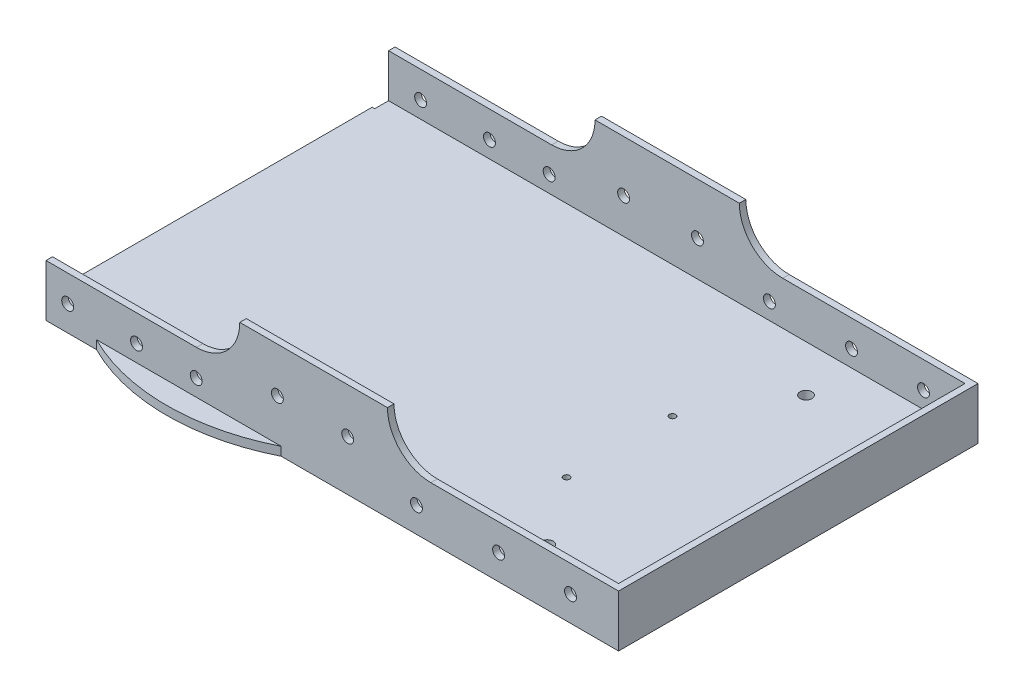
SolidWorks part; units mm, degrees
ref_plane "Front Plane" through (0, 0, 0) normal (0, 0, 1) x (1, 0, 0)
ref_plane "Top Plane" through (0, 0, 0) normal (0, 1, 0) x (1, 0, 0)
ref_plane "Right Plane" through (0, 0, 0) normal (1, 0, 0) x (0, 0, -1)
sketch "Sketch1" plane through (0, 0, 0) normal (0, 1, 0) x (1, 0, 0)
  line L1 (0, 0) -> (278.0499, 0)
  line L2 (0, 0) -> (0, 166.0007)
  line L3 (0, 166.0007) -> (278.0499, 166.0007)
  line L4 (278.0499, 0) -> (278.0499, 166.0007)
extrude "Boss-Extrude1" add sketch "Sketch1" along normal blind 24
sketch "Sketch2" plane through (0, 0, 0) normal (0, -1, 0) x (-1, 0, 0)
  line L1 (-7.6506, 156.6405) -> (14.2402, 156.6405)
  line L2 (-7.6506, 156.6405) -> (-7.6506, 11.5417)
  line L3 (-7.6506, 11.5417) -> (14.2402, 11.5417)
  line L4 (14.2402, 156.6405) -> (14.2402, 11.5417)
extrude "Cut-Extrude1" cut sketch "Sketch2" against normal through all
sketch "Sketch3" plane through (0, 24, 0) normal (0, 1, 0) x (1, 0, 0)
  line L0 (226.9955, 0) -> (226.9955, 3) construction
  line L1 (0, 0) -> (278.0499, 0) construction
  line L2 (278.0499, 166.0007) -> (278.0499, 163.0007) construction
  line L3 (278.0499, 0) -> (278.0499, 166.0007) construction
  line L4 (0, 155.7398) -> (3, 155.7398) construction
  line L5 (0, 166.0007) -> (0, 156.6405) construction
  line L6 (278.0499, 22.4963) -> (275.0499, 22.4963) construction
  line L7 (275.0499, 163.0007) -> (275.0499, 3)
  line L8 (275.0499, 3) -> (3, 3)
  line L9 (3, 3) -> (3, 163.0007)
  line L10 (3, 163.0007) -> (275.0499, 163.0007)
extrude "Cut-Extrude2" cut sketch "Sketch3" against normal blind 20
sketch "Sketch4" plane through (0, 24, 0) normal (0, 1, 0) x (1, 0, 0)
  line L0 (0, 0) -> (278.0499, 0) construction
  line L1 (171.3453, 0) -> (103.1403, 0)
  line L2 (171.3453, 0) -> (171.3453, 3)
  line L3 (171.3453, 3) -> (103.1403, 3)
  line L4 (103.1403, 0) -> (103.1403, 3)
  line L5 (3, 3) -> (275.0499, 3) construction
extrude "Boss-Extrude2" add sketch "Sketch4" along normal blind 20
fillet "Fillet4" radius 20 1 edges at (103.1403, 24, -1.5) type face fillet first side face at (103.1403, 34, -1.5) second side face at (35.3801, 24, -4.8472)
fillet "Fillet5" radius 20 1 edges at (171.3453, 24, -1.5) type face fillet first side face at (145.489, 24, -97.7284) second side face at (171.3453, 34, -1.5)
sketch "Sketch5" plane through (0, 24, 0) normal (0, 1, 0) x (1, 0, 0)
  line L0 (278.0499, 166.0007) -> (0, 166.0007) construction
  line L1 (104.1867, 166.0007) -> (170.8443, 166.0007)
  line L2 (104.1867, 166.0007) -> (104.1867, 163.0007)
  line L3 (104.1867, 163.0007) -> (170.8443, 163.0007)
  line L4 (170.8443, 166.0007) -> (170.8443, 163.0007)
  line L5 (275.0499, 163.0007) -> (3, 163.0007) construction
extrude "Boss-Extrude3" add sketch "Sketch5" along normal blind 20
fillet "Fillet6" radius 20 1 edges at (104.1867, 24, -164.5007) type face fillet first side face at (104.1867, 34, -164.5007) second side face at (35.7289, 24, -161.8806)
fillet "Fillet7" radius 20 1 edges at (170.8443, 24, -164.5007) type face fillet first side face at (170.8443, 34, -164.5007) second side face at (228.8223, 24, -83.0003)
sketch "Sketch6" plane through (0, 0, -163.0007) normal (0, 0, 1) x (1, 0, 0)
  circle A0 centre (151.5064, 20.306) radius 2.75
  circle A1 centre (117.3926, 20.306) radius 2.75
extrude "HolesForBolts1" cut sketch "Sketch6" against normal through all
sketch "Sketch7" plane through (0, 0, -166.0007) normal (0, 0, -1) x (-1, 0, 0)
  circle A0 centre (-23.6542, 11.6758) radius 2.75
  circle A1 centre (-55.4415, 11.6758) radius 2.75
  circle A2 centre (-83.0044, 11.6758) radius 2.75
  circle A3 centre (-184.7276, 11.6758) radius 2.75
  circle A4 centre (-222.6455, 11.6758) radius 2.75
  circle A5 centre (-255.8817, 11.6758) radius 2.75
extrude "Cut-Extrude4" cut sketch "Sketch7" against normal through all
sketch "Sketch8" plane through (0, 0, -3) normal (0, 0, -1) x (-1, 0, 0)
  circle A0 centre (-120.4871, 23.2804) radius 2.75
  circle A1 centre (-152.9663, 23.2804) radius 2.75
extrude "Cut-Extrude5" cut sketch "Sketch8" against normal blind 20
ref_plane "Plane1" through (0, 0, -11.5417) normal (0, 0, 1) x (1, 0, 0)
sketch "Sketch11" plane through (0, 0, 0) normal (0, -1, 0) x (1, 0, 0)
  line L0 (7.6506, -11.5417) -> (0, -11.5417) construction
  line L1 (0, 0) -> (13.6461, 0)
  line L2 (0, 0) -> (0, -11.5417)
  line L3 (0, -11.5417) -> (13.6461, -11.5417)
  line L4 (13.6461, 0) -> (13.6461, -11.5417)
extrude "Cut-Extrude6" cut sketch "Sketch11" against normal through all
sketch "Sketch12" plane through (0, 0, 0) normal (0, -1, 0) x (1, 0, 0)
  line L0 (0, -156.6405) -> (7.6506, -156.6405) construction
  line L1 (0, -166.0007) -> (8.8441, -166.0007)
  line L2 (0, -166.0007) -> (0, -156.6405)
  line L3 (0, -156.6405) -> (8.8441, -156.6405)
  line L4 (8.8441, -166.0007) -> (8.8441, -156.6405)
extrude "Cut-Extrude7" cut sketch "Sketch12" against normal through all
sketch "HolesInLidForPiCover" plane through (0, 0, 0) normal (0, -1, 0) x (1, 0, 0)
  circle A0 centre (223.0138, -141.6086) radius 2.75
  circle A1 centre (223.0138, -22.1297) radius 2.75
extrude "Cut-Extrude8" cut sketch "HolesInLidForPiCover" against normal up to surface (4 mm away) up to face at (76.2977, 4, -83.5457)
ref_point "RasPiBoltPoint1"
ref_point "RasPiBoltPoint2"
ref_point "RasPiBoltPoint3"
ref_point "RasPiBoltPoint4"
sketch "LidHolesForPi" plane through (0, 0, 0) normal (0, -1, 0) x (1, 0, 0)
  circle A0 centre (200.5621, -102.3707) radius 1.455
  circle A1 centre (200.5621, -53.5029) radius 1.455
  circle A2 centre (258.5449, -53.5029) radius 1.455
  circle A3 centre (258.5449, -102.3707) radius 1.455
extrude "Cut-Extrude9" cut sketch "LidHolesForPi" against normal up to surface (4 mm away) up to face at (223.0138, 4, -24.8797)
ref_point "LidHoleForCoverLocation1"
ref_point "LidHoleForCoverLocation2"
sketch "Sketch14" plane through (0, 0, 0) normal (0, -1, 0) x (1, 0, 0)
  circle A0 centre (264.7636, -18.9201) radius 2.75
  circle A1 centre (181.6168, -18.9187) radius 2.75
extrude "Cut-Extrude10" cut sketch "Sketch14" against normal up to surface (4 mm away) up to face at (258.5449, 4, -54.9579)
sketch "Sketch15" plane through (0, 0, 0) normal (0, -1, 0) x (1, 0, 0)
  circle A0 centre (79.5908, -84.8811) radius 95
extrude "Boss-Extrude4" add sketch "Sketch15" against normal up to surface (4 mm away) up to face at (181.6168, 4, -21.6687)
sketch "Sketch16" plane through (0, 0, 0) normal (0, -1, 0) x (1, 0, 0)
  line L1 (7.6506, -22.8359) -> (-30.4108, -22.8359)
  line L2 (7.6506, -22.8359) -> (7.6506, -147.5505)
  line L3 (7.6506, -147.5505) -> (-30.4108, -147.5505)
  line L4 (-30.4108, -22.8359) -> (-30.4108, -147.5505)
extrude "Cut-Extrude11" cut sketch "Sketch16" against normal up to surface (4 mm away) up to face at (60.2623, 4, -83.8128)
